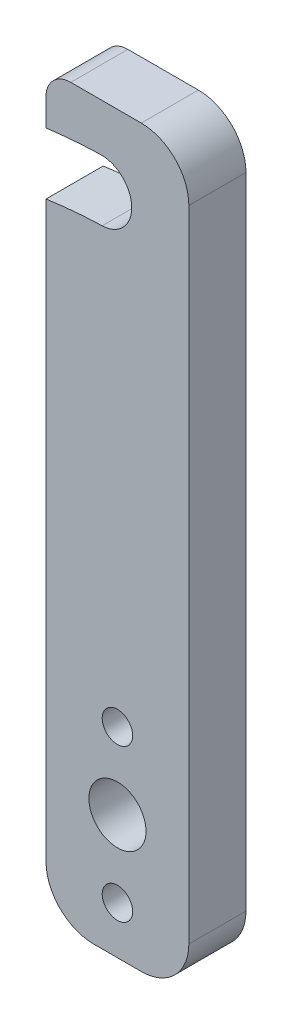
SolidWorks part; units mm, degrees
material "MDF"
ref_plane "Plano frontal" through (0, 0, 0) normal (0, 0, 1) x (1, 0, 0)
ref_plane "Plano superior" through (0, 0, 0) normal (0, 1, 0) x (1, 0, 0)
ref_plane "Plano direito" through (0, 0, 0) normal (1, 0, 0) x (0, 0, -1)
sketch "Esboço1" plane through (0, 0, 0) normal (0, 0, 1) x (1, 0, 0)
  line L0 (0, -17.5864) -> (0, -33.5864) construction
  line L1 (-7.5, -38.5864) -> (7.5, -38.5864)
  line L2 (-7.5, -38.5864) -> (-7.5, 38.5864)
  line L3 (-7.5, 38.5864) -> (7.5, 38.5864)
  line L4 (7.5, -38.5864) -> (7.5, 38.5864)
  line L5 (-7.5, -38.5864) -> (7.5, 38.5864) construction
  line L6 (-7.5, 38.5864) -> (7.5, -38.5864) construction
  circle A0 centre (0, -33.5864) radius 1.6
  circle A1 centre (0, -17.5864) radius 1.6
  arc A3 (-1.6985, 30.3879) -> (-7.9545, 29.8458) centre (0, -25.5864) ccw construction
  arc A4 (-1.7956, 33.5864) -> (-8.4091, 33.0133) centre (0, -25.5864) ccw
  arc A5 (-1.6015, 27.1893) -> (-7.5, 26.6782) centre (0, -25.5864) ccw
  arc A6 (-1.6015, 27.1893) -> (-1.7956, 33.5864) centre (-1.6985, 30.3879) ccw
  arc A7 (-8.4091, 33.0133) -> (-7.5, 26.6782) centre (-7.9545, 29.8458) ccw
  circle A8 centre (0, -25.5864) radius 3
  point P0 (0, 0)
  point P14 (-4.8341, 30.2046)
  point P20 (1.5, 30.4849)
  dimension "D1" = 56
  dimension "D2" = 3.2
  dimension "D4" = 16
  dimension "D6" = 3.2
  dimension "D8" = 6
  dimension "D3" = 15
  dimension "D5" = 5
  dimension "D7" = 5
  dimension "D9" = 6
extrude "Ressalto-extrusão1" add sketch "Esboço1" along normal blind 6 contours A6 A5 L2 L1 L4 L3 A4 A1 A0 region at (0.1671, -0.4523, 0)
fillet "Filete1" radius 5 3 edges at (-7.5, -38.5864, 3) (7.5, -38.5864, 3) (7.5, 38.5864, 3)
fillet "Filete2" radius 2.6 1 edges at (-7.5, 38.5864, 3)
